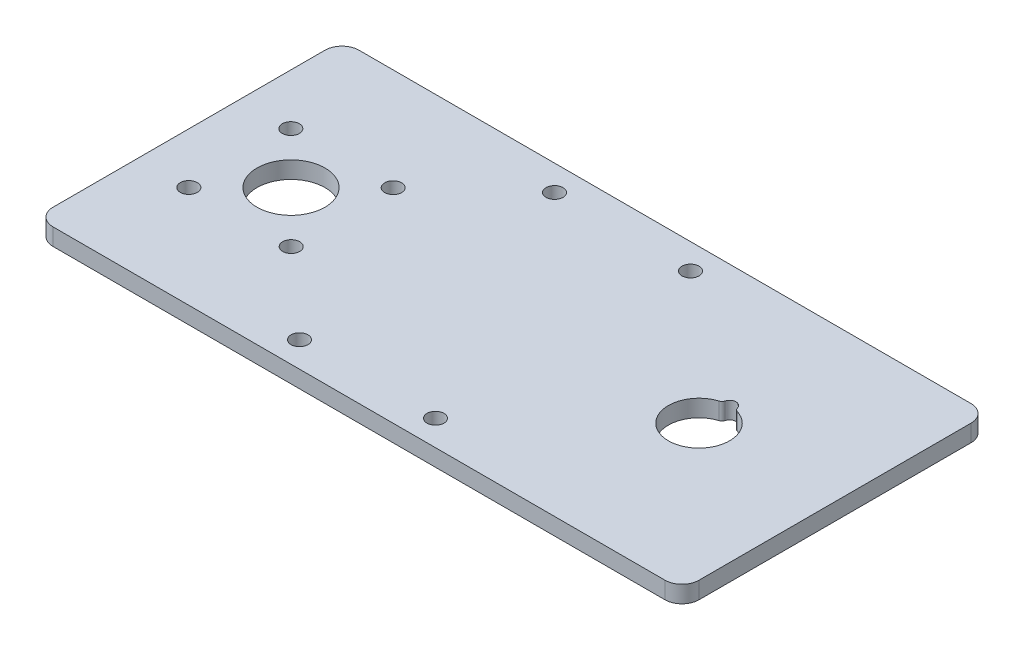
SolidWorks part; units mm, degrees
material "PC High Viscosity"
ref_plane "Front Plane" through (0, 0, 0) normal (0, 0, 1) x (1, 0, 0)
ref_plane "Top Plane" through (0, 0, 0) normal (0, 1, 0) x (1, 0, 0)
ref_plane "Right Plane" through (0, 0, 0) normal (1, 0, 0) x (0, 0, -1)
sketch "Sketch1" plane through (0, 0, 0) normal (0, 1, 0) x (1, 0, 0)
  line L1 (0, 0) -> (241.3, 0)
  line L2 (0, 0) -> (0, 114.3)
  line L3 (0, 114.3) -> (241.3, 114.3)
  line L4 (241.3, 0) -> (241.3, 114.3)
  circle A0 centre (38.1, 57.15) radius 12.7
  arc A1 (188.1317, 68.332) -> (192.8683, 68.332) centre (190.5, 57.15) ccw
  circle A2 centre (88.9, 104.775) radius 3.175
  circle A3 centre (139.7, 104.775) radius 3.175
  circle A4 centre (139.7, 9.525) radius 3.175
  circle A5 centre (88.9, 9.525) radius 3.175
  circle A6 centre (18.984, 76.2) radius 3.175
  circle A7 centre (18.984, 38.1) radius 3.175
  circle A8 centre (57.216, 38.1) radius 3.175
  circle A9 centre (57.216, 76.2) radius 3.175
  arc A10 (192.8683, 68.332) -> (188.1317, 68.332) centre (190.5, 68.58) ccw
  dimension "D1" = 25.4
  dimension "D2" = 22.86
  dimension "D9" = 6.35
  dimension "D15" = 6.35
  dimension "D19" = 4.7625
  dimension "D3" = 114.3
  dimension "D4" = 57.15
  dimension "D5" = 57.15
  dimension "D6" = 241.3
  dimension "D7" = 38.1
  dimension "D8" = 190.5
  dimension "D10" = 50.8
  dimension "D11" = 9.525
  dimension "D12" = 9.525
  dimension "D13" = 88.9
  dimension "D14" = 26.9875
  dimension "D16" = 26.9875
  dimension "D17" = 26.9875
  dimension "D18" = 38.1
extrude "Boss-Extrude1" add sketch "Sketch1" along normal blind 6.35
fillet "Fillet1" radius 6.35 4 edges at (0, 3.175, -114.3) (241.3, 3.175, -114.3) (241.3, 3.175, 0) (0, 3.175, 0)
fillet "Fillet2" radius 1.5875 2 edges at (188.1317, 3.175, -68.332) (192.8683, 3.175, -68.332)
